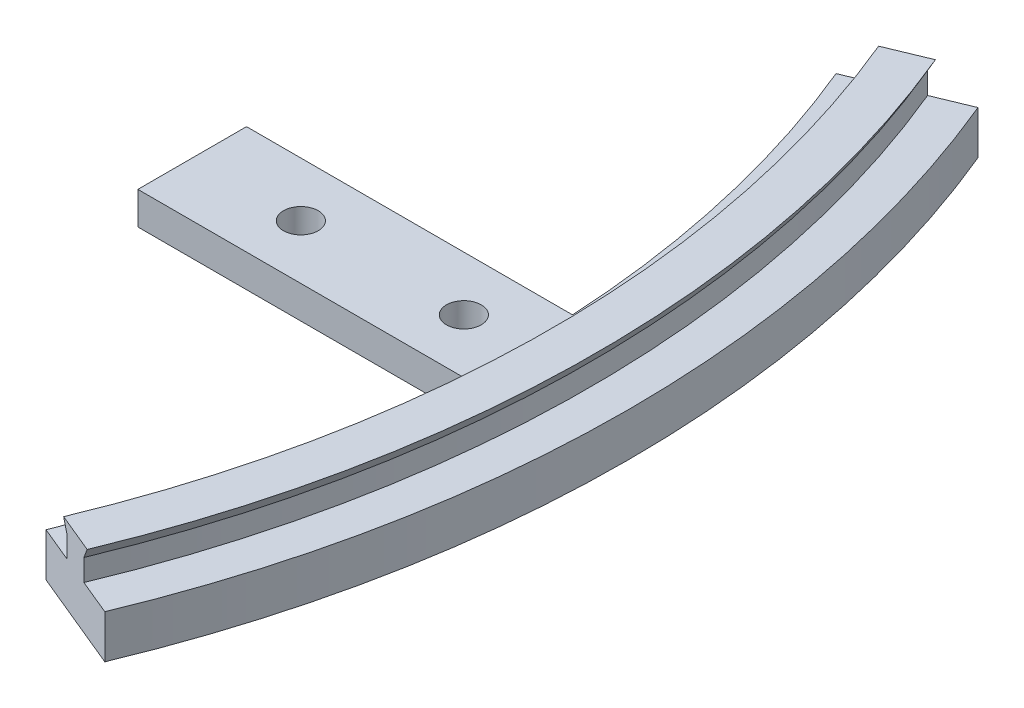
SolidWorks part; units mm, degrees
ref_plane "Front Plane" through (0, 0, 0) normal (0, 0, 1) x (1, 0, 0)
ref_plane "Top Plane" through (0, 0, 0) normal (0, 1, 0) x (1, 0, 0)
ref_plane "Right Plane" through (0, 0, 0) normal (1, 0, 0) x (0, 0, -1)
ref_axis "Axis1" through (0, -0.2847, 0) along (0, 1, 0)
sketch "Sketch1" plane through (0, 0, 0) normal (0, 0, 1) x (1, 0, 0)
  line L0 (105, 0) -> (105, 4)
  line L1 (105, 4) -> (101.45, 4)
  line L2 (101.45, 4) -> (101.45, 6)
  line L3 (98.55, 6) -> (98, 7)
  line L4 (98.55, 6) -> (98.55, 4)
  line L5 (98.55, 4) -> (95, 4)
  line L6 (95, 4) -> (95, 0)
  line L7 (95, 0) -> (105, 0)
  line L8 (98, 7) -> (102, 7)
  line L9 (102, 7) -> (101.45, 6)
  point P9 (100, 0)
  dimension "D1" = 4
  dimension "D2" = 10
  dimension "D3" = 3.55
  dimension "D4" = 100
  dimension "D5" = 4
  dimension "D6" = 2
  dimension "D7" = 3
revolve "Revolve1" add sketch "Sketch1" angle 45 mid plane about axis through (0, -0.2847, 0) along (0, 1, 0)
sketch "Sketch2" plane through (0, 4, 0) normal (0, -1, 0) x (-1, 0, 0)
  line L0 (-64.8683, -5) -> (-64.8683, 5)
  line L1 (-94.8683, -5) -> (-64.8683, -5)
  line L2 (-87.7686, -36.3549) -> (-87.7686, 36.3549) construction
  line L3 (-94.8683, 5) -> (-64.8683, 5)
  line L4 (0, 0) -> (-500, 207.1068) construction
  line L5 (0, 0) -> (-500, -207.1068) construction
  line L6 (-97.0074, 40.1818) -> (-93.7276, 38.8232) construction
  line L7 (-87.7686, -36.3549) -> (-97.0074, -40.1818) construction
  line L8 (-500, 207.1068) -> (-500, -207.1068) construction
  arc A2 (-94.8683, -5) -> (-94.8683, 5) centre (0, 0) cw
  arc A3 (-87.7686, 36.3549) -> (-87.7686, -36.3549) centre (0, 0) ccw construction
  point P4 (0, 0)
  point P7 (0, 0)
  dimension "D1" = 10
  dimension "D2" = 30
  dimension "D3" = 5
  dimension "D4" = 72.7099
  dimension "D5" = 500
  dimension "D6" = 414.2136
extrude "Boss-Extrude1" add sketch "Sketch2" along normal blind 3
sketch "Sketch3" plane through (0, 1, 0) normal (0, -1, 0) x (-1, 0, 0)
  line L0 (-64.8683, -5) -> (-64.8683, 5) construction
  line L1 (-64.8683, -1.45) -> (-94.9889, -1.45)
  line L2 (-64.8683, -1.45) -> (-64.8683, 1.45)
  line L3 (-64.8683, 1.45) -> (-94.9889, 1.45)
  line L4 (-94.9889, -1.45) -> (-94.9889, 1.45)
  line L5 (-94.8683, -5) -> (-64.8683, -5) construction
  circle A0 centre (-67.2512, 0) radius 50 construction
  arc A1 (-94.8683, 5) -> (-94.8683, -5) centre (0, 0) ccw construction
  dimension "D4" = 100
  dimension "D1" = 2.9
  dimension "D2" = 3.55
extrude "Boss-Extrude2" add sketch "Sketch3" along normal blind 1 separate body
sketch "Sketch4" plane through (0, 4, 0) normal (0, 1, 0) x (1, 0, 0)
  line L0 (64.8683, -5) -> (64.8683, 5) construction
  circle A0 centre (74.8683, 0) radius 1.6
  circle A1 centre (89.8683, 0) radius 1.6
  point P7 (64.8683, 0)
  dimension "D1" = 3.2
  dimension "D2" = 10
  dimension "D3" = 25
extrude "Cut-Extrude1" cut sketch "Sketch4" against normal through all
ref_plane "Plane1" through (70, 0, 0) normal (1, 0, 0) x (0, 0, -1)
